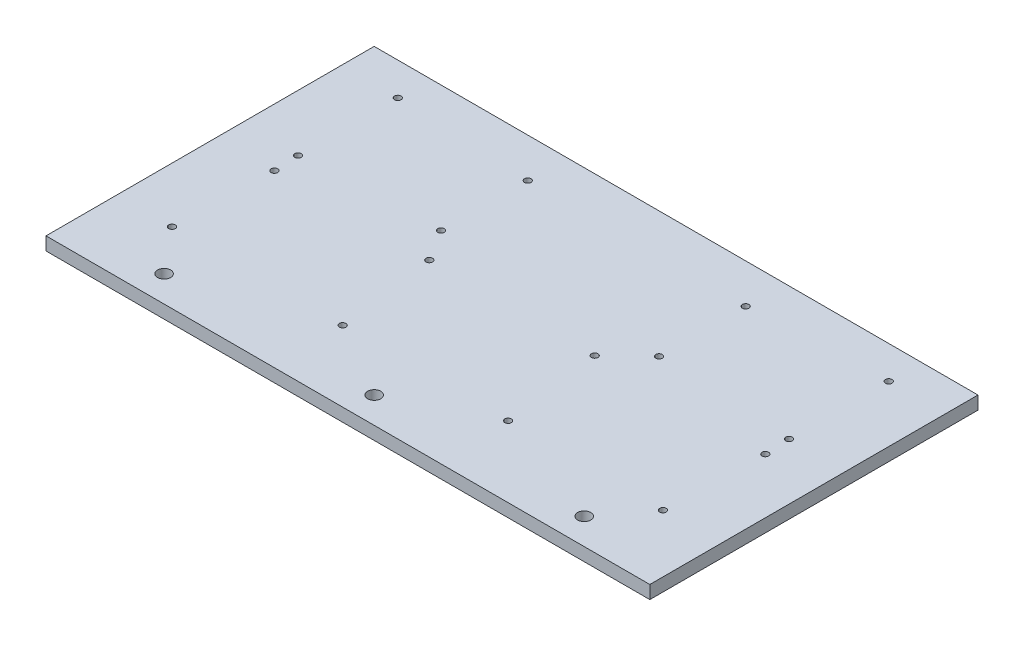
SolidWorks part; units mm, degrees
ref_plane "Front Plane" through (0, 0, 0) normal (0, 0, 1) x (1, 0, 0)
ref_plane "Top Plane" through (0, 0, 0) normal (0, 1, 0) x (1, 0, 0)
ref_plane "Right Plane" through (0, 0, 0) normal (1, 0, 0) x (0, 0, -1)
sketch "Sketch1" plane through (0, 0, 0) normal (0, 1, 0) x (1, 0, 0)
  line L1 (0, 0) -> (292.1, 0)
  line L2 (0, 0) -> (0, 158.75)
  line L3 (0, 158.75) -> (292.1, 158.75)
  line L4 (292.1, 0) -> (292.1, 158.75)
  dimension "D1" = 292.1
  dimension "D2" = 158.75
extrude "Boss-Extrude1" add sketch "Sketch1" along normal blind 6.35
sketch "Sketch2" plane through (0, 6.35, 0) normal (0, 1, 0) x (1, 0, 0)
  line L0 (0, 25.4) -> (292.1, 25.4) construction
  line L1 (0, 12.7) -> (292.1, 12.7) construction
  line L2 (146.05, 0) -> (146.05, 158.75) construction
  line L4 (0, 158.75) -> (0, 0)
  line L5 (0, 0) -> (292.1, 0)
  line L6 (292.1, 0) -> (292.1, 158.75)
  line L7 (292.1, 158.75) -> (0, 158.75)
  line L8 (0, 158.75) -> (0, 0) construction
  line L9 (0, 0) -> (292.1, 0) construction
  line L10 (292.1, 0) -> (292.1, 158.75) construction
  line L11 (292.1, 158.75) -> (0, 158.75) construction
  circle A0 centre (146.05, 12.7) radius 3.175
  circle A1 centre (247.65, 12.7) radius 3.175
  circle A2 centre (44.45, 12.7) radius 3.175
  dimension "D6" = 6.35
  dimension "D7" = 6.35
  dimension "D8" = 6.35
  dimension "D2" = 25.4
  dimension "D3" = 12.7
  dimension "D4" = 101.6
  dimension "D5" = 101.6
  dimension "D1" = 0
extrude "Cut-Extrude2" cut sketch "Sketch2" against normal blind 6.35
sketch "Sketch4" plane through (0, 6.35, 0) normal (0, 1, 0) x (1, 0, 0)
  line L4 (279.4, 85.09) -> (177.8, 85.09)
  line L5 (177.8, 85.09) -> (177.8, 31.75)
  line L6 (177.8, 31.75) -> (279.4, 31.75)
  line L7 (279.4, 31.75) -> (279.4, 85.09)
  line L8 (279.4, 85.09) -> (177.8, 85.09) construction
  line L9 (177.8, 85.09) -> (177.8, 31.75) construction
  line L10 (177.8, 31.75) -> (279.4, 31.75) construction
  line L11 (279.4, 31.75) -> (279.4, 85.09) construction
  line L160 (114.3, 31.75) -> (114.3, 85.09)
  line L161 (114.3, 85.09) -> (12.7, 85.09)
  line L162 (12.7, 85.09) -> (12.7, 31.75)
  line L163 (12.7, 31.75) -> (114.3, 31.75)
  line L164 (114.3, 31.75) -> (114.3, 85.09) construction
  line L165 (114.3, 85.09) -> (12.7, 85.09) construction
  line L166 (12.7, 85.09) -> (12.7, 31.75) construction
  line L167 (12.7, 31.75) -> (114.3, 31.75) construction
  circle A1 centre (182.88, 82.55) radius 1.5875
  circle A2 centre (182.88, 82.55) radius 1.5875
  circle A3 centre (189.23, 34.29) radius 1.5875
  circle A4 centre (189.23, 34.29) radius 1.5875
  circle A5 centre (265.43, 82.55) radius 1.5875
  circle A6 centre (265.43, 82.55) radius 1.5875
  circle A7 centre (264.16, 34.29) radius 1.5875
  circle A8 centre (264.16, 34.29) radius 1.5875
  circle A9 centre (264.795, 142.875) radius 1.5875
  circle A10 centre (264.795, 142.875) radius 1.5875
  circle A11 centre (264.795, 94.615) radius 1.5875
  circle A12 centre (264.795, 94.615) radius 1.5875
  circle A13 centre (198.755, 97.79) radius 1.5875
  circle A14 centre (198.755, 97.79) radius 1.5875
  circle A15 centre (198.755, 139.7) radius 1.5875
  circle A16 centre (198.755, 139.7) radius 1.5875
  circle A313 centre (102.87, 82.55) radius 1.5875
  circle A314 centre (102.87, 82.55) radius 1.5875
  circle A315 centre (109.22, 34.29) radius 1.5875
  circle A316 centre (109.22, 34.29) radius 1.5875
  circle A317 centre (26.67, 34.29) radius 1.5875
  circle A318 centre (26.67, 34.29) radius 1.5875
  circle A319 centre (27.94, 82.55) radius 1.5875
  circle A320 centre (27.94, 82.55) radius 1.5875
  circle A321 centre (93.345, 139.7) radius 1.5875
  circle A322 centre (93.345, 139.7) radius 1.5875
  circle A323 centre (93.345, 97.79) radius 1.5875
  circle A324 centre (93.345, 97.79) radius 1.5875
  circle A325 centre (27.305, 142.875) radius 1.5875
  circle A326 centre (27.305, 142.875) radius 1.5875
  circle A327 centre (27.305, 94.615) radius 1.5875
  circle A328 centre (27.305, 94.615) radius 1.5875
  dimension "D1" = 0
  dimension "D2" = 0
  dimension "D3" = 0
  dimension "D4" = 0
  dimension "D5" = 0
  dimension "D6" = 0
  dimension "D7" = 0
  dimension "D8" = 0
  dimension "D9" = 0
  dimension "D10" = 0
  dimension "D11" = 0
  dimension "D12" = 0
  dimension "D13" = 0
  dimension "D14" = 0
  dimension "D15" = 0
  dimension "D16" = 0
  dimension "D17" = 0
  dimension "D18" = 0
extrude "Cut-Extrude3" cut sketch "Sketch4" against normal through all
equation "\"D5@Sketch2\"=\"D4@Sketch2\""
equation "\"D7@Sketch2\"=\"D6@Sketch2\""
equation "\"D8@Sketch2\"=\"D7@Sketch2\""
